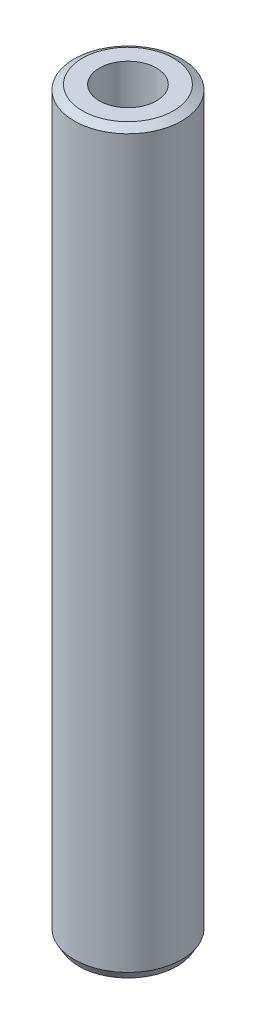
SolidWorks part; units mm, degrees
ref_plane "Front Plane" through (0, 0, 0) normal (0, 0, 1) x (1, 0, 0)
ref_plane "Top Plane" through (0, 0, 0) normal (0, 1, 0) x (1, 0, 0)
ref_plane "Right Plane" through (0, 0, 0) normal (1, 0, 0) x (0, 0, -1)
sketch "Sketch1" plane through (0, 0, 0) normal (0, 1, 0) x (1, 0, 0)
  circle A0 centre (0, 0) radius 5
  dimension "SHAFT_OD" = 10
extrude "Boss-Extrude1" add sketch "Sketch1" along normal blind 68.7097
sketch "Sketch2" plane through (0, 0, 0) normal (0, 1, 0) x (1, 0, 0)
  circle A0 centre (0, 0) radius 2.6517
  dimension "BORE_D" = 5.3033
extrude "Cut-Extrude1" cut sketch "Sketch2" along normal through all
chamfer "Chamfer1" distance 0.4393 angle 60 2 edges at (0, 68.7097, 5) (0, 0, 5) first distance on face at (0, 68.7097, 5) first distance on face at (0, 0, 2.6517)
